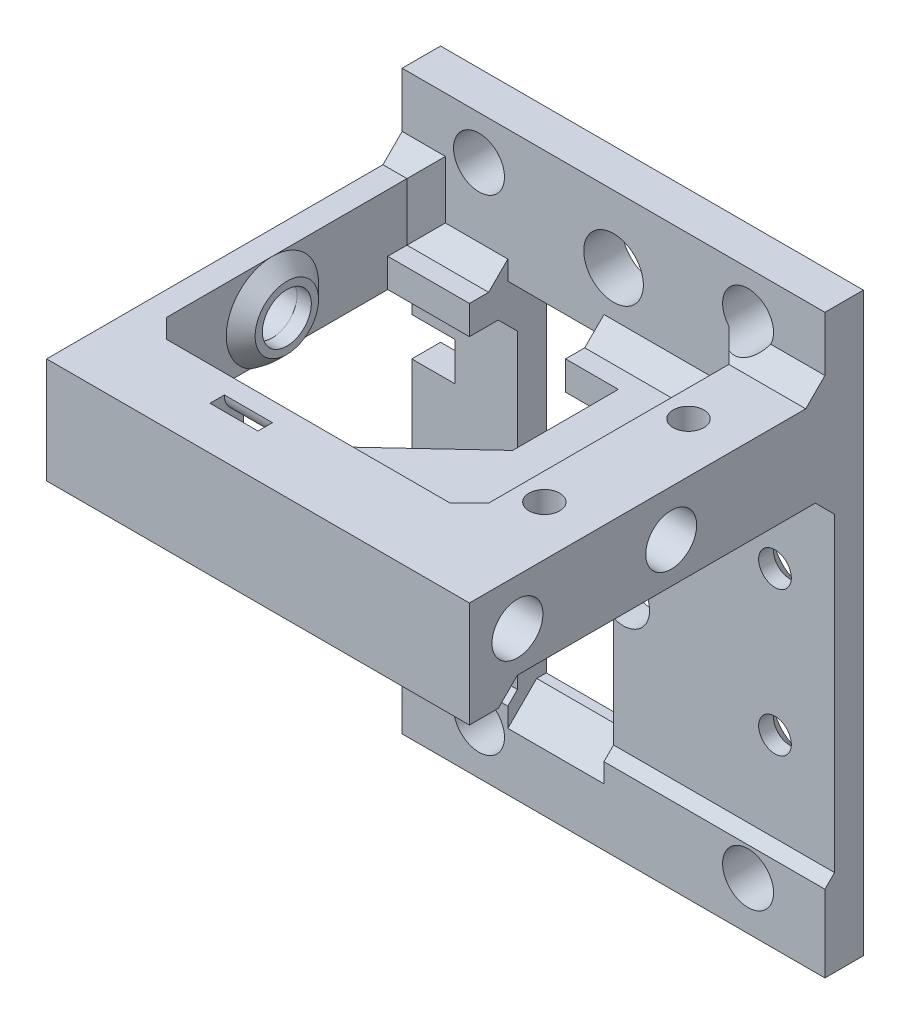
SolidWorks part; units mm, degrees
ref_plane "Front Plane" through (0, 0, 0) normal (0, 0, 1) x (1, 0, 0)
ref_plane "Top Plane" through (0, 0, 0) normal (0, 1, 0) x (1, 0, 0)
ref_plane "Right Plane" through (0, 0, 0) normal (1, 0, 0) x (0, 0, -1)
sketch "Sketch1" plane through (0, 0, 0) normal (0, 1, 0) x (1, 0, 0)
  line L0 (-19.5, 12.5) -> (-19.5, -12.5)
  line L1 (-22, -20.5) -> (22, -20.5)
  line L2 (-22, -20.5) -> (-22, 20.5)
  line L3 (-22, 20.5) -> (22, 20.5)
  line L4 (22, -20.5) -> (22, 20.5)
  line L5 (-22, -20.5) -> (22, 20.5) construction
  line L6 (-22, 20.5) -> (22, -20.5) construction
  line L7 (-19.5, 12.5) -> (4.5, 12.5)
  line L8 (4.5, 12.5) -> (4.5, 1.5)
  line L9 (-19.5, -12.5) -> (-10.5244, -12.5)
  line L10 (-10.5244, -12.5) -> (4.5, 1.5)
  circle A0 centre (16.8, -7.5) radius 1.6
  circle A1 centre (16.8, 7.5) radius 1.6
  point P0 (0, 0)
  dimension "D9" = 3.2
  dimension "D12" = 3.2
  dimension "D1" = 44
  dimension "D2" = 41
  dimension "D3" = 2.5
  dimension "D4" = 25
  dimension "D5" = 8
  dimension "D6" = 24
  dimension "D7" = 11
  dimension "D8" = 5.2
  dimension "D10" = 13
  dimension "D11" = 15
extrude "Boss-Extrude1" add sketch "Sketch1" along normal blind 3
sketch "Sketch2" plane through (0, 3, 0) normal (0, 1, 0) x (1, 0, 0)
  line L0 (-22, 20.5) -> (-22, -20.5) construction
  line L1 (22, 20.5) -> (-22, 20.5)
  line L2 (22, 20.5) -> (22, 16.5)
  line L3 (22, 16.5) -> (-22, 16.5)
  line L4 (-22, 20.5) -> (-22, 16.5)
  dimension "D1" = 4
extrude "Boss-Extrude2" add sketch "Sketch2" along normal blind 13.7
sketch "Sketch3" plane through (0, 0, 0) normal (0, -1, 0) x (1, 0, 0)
  line L0 (22, 20.5) -> (22, -20.5) construction
  line L1 (-22, -20.5) -> (22, -20.5)
  line L2 (-22, -20.5) -> (-22, -17.5)
  line L3 (-22, -17.5) -> (22, -17.5)
  line L4 (22, -20.5) -> (22, -17.5)
  dimension "D1" = 3
extrude "Boss-Extrude3" add sketch "Sketch3" along normal blind 41.3
sketch "Sketch4" plane through (0, 0, 0) normal (0, -1, 0) x (1, 0, 0)
  line L0 (-22, -17.5) -> (-22, 20.5) construction
  line L1 (22, 20.5) -> (-22, 20.5)
  line L2 (22, 20.5) -> (22, 17.5)
  line L3 (22, 17.5) -> (-22, 17.5)
  line L4 (-22, 20.5) -> (-22, 17.5)
  dimension "D1" = 3
extrude "Boss-Extrude4" add sketch "Sketch4" along normal blind 32.5
sketch "Sketch8" plane through (-22, 0, 0) normal (-1, 0, 0) x (0, 0, 1)
  line L0 (-16.5, -35.3) -> (-17.5, -34.3)
  line L1 (-17.5, -41.3) -> (-16.5, -41.3)
  line L2 (-17.5, -41.3) -> (-17.5, -35.3)
  line L3 (-17.5, -35.3) -> (-16.5, -35.3)
  line L4 (-16.5, -41.3) -> (-16.5, -35.3)
  line L5 (-17.5, -41.3) -> (-17.5, 0) construction
  line L6 (-17.5, -34.3) -> (-17.5, -35.3)
  line M5 (-17.5, -41.3) -> (-17.5, 0)
  dimension "D1" = 1
  dimension "D2" = 6
extrude "Boss-Extrude6" add sketch "Sketch8" against normal up to surface (44 mm away) contours L1 L4 L3 M5 | L3 L0 M5 region at (-22, -34.9667, -17.1667) region at (-22, -38.3, -17) up to face at (22, -10.82, -3.3)
sketch "Sketch9" plane through (0, 0, 20.5) normal (0, 0, 1) x (1, 0, 0)
  line L0 (-22, 3) -> (-22, -32.5) construction
  line L1 (3, -26) -> (10, -26)
  line L2 (3, -26) -> (3, -5)
  line L3 (3, -5) -> (10, -5)
  line L4 (10, -26) -> (10, -5)
  line L5 (22, -32.5) -> (-22, -32.5) construction
  line L6 (22, 3) -> (22, -32.5) construction
  circle A0 centre (15.8, -10) radius 1.6
  circle A1 centre (15.8, -25) radius 1.6
  dimension "D5" = 3.2
  dimension "D6" = 3.2
  dimension "D1" = 25
  dimension "D2" = 7
  dimension "D3" = 21
  dimension "D4" = 6.5
  dimension "D7" = 6.2
  dimension "D8" = 6.2
  dimension "D9" = 15
  dimension "D10" = 7.5
extrude "Cut-Extrude2" cut sketch "Sketch9" against normal up to next
sketch "Sketch12" plane through (0, 3, 0) normal (0, 1, 0) x (1, 0, 0)
  line L0 (-22, 16.5) -> (-22, -20.5) construction
  line L1 (22, -20.5) -> (-22, -20.5)
  line L2 (22, -20.5) -> (22, -12.5)
  line L3 (22, -12.5) -> (-22, -12.5)
  line L4 (-22, -20.5) -> (-22, -12.5)
  line L5 (-19.5, -12.5) -> (-10.5244, -12.5) construction
  line L6 (-19.5, 12.5) -> (-19.5, -12.5) construction
  line L7 (-22, 16.5) -> (-19.5, 16.5)
  line L8 (-22, 16.5) -> (-22, -12.5)
  line L9 (-22, -12.5) -> (-19.5, -12.5)
  line L10 (-19.5, 16.5) -> (-19.5, -12.5)
  line L11 (-22, 16.5) -> (22, 16.5) construction
  line L12 (22, -12.5) -> (14, -12.5)
  line L13 (22, -12.5) -> (22, 16.5)
  line L14 (22, 16.5) -> (14, 16.5)
  line L15 (14, -12.5) -> (14, 16.5)
  circle M6 centre (16.8, 7.5) radius 1.6
  circle M7 centre (16.8, -7.5) radius 1.6
  line M11 (-10.5244, -12.5) -> (-19.5, -12.5)
  line M12 (-19.5, -12.5) -> (-19.5, 12.5)
  line M13 (22, 16.5) -> (-22, 16.5)
  line M14 (-22, 16.5) -> (-22, -20.5)
  line M15 (-22, -20.5) -> (22, -20.5)
  line M16 (22, -20.5) -> (22, 16.5)
  dimension "D1" = 8
extrude "Boss-Extrude7" add sketch "Sketch12" along normal blind 6 contours L15 L3 M16 M13 M7 M6 | L3 M16 M11 M14 M15 | L10 L3 M13 M14 M12 region at (0, 3, 16.5) region at (18.0894, 3, -2.149) region at (-20.75, 3, -2)
sketch "Sketch13" plane through (-22, 0, 0) normal (-1, 0, 0) x (0, 0, 1)
  line L0 (20.5, 9) -> (20.5, -32.5) construction
  line L1 (-17.5, 0) -> (17.5, 0) construction
  line L2 (-17.5, -34.3) -> (-17.5, 0) construction
  circle A0 centre (15.5, 4.2) radius 2.65
  circle A1 centre (-0.5, 4.2) radius 2.65
  dimension "D3" = 5.3
  dimension "D5" = 5.3
  dimension "D1" = 5
  dimension "D2" = 4.2
  dimension "D4" = 17
extrude "Cut-Extrude3" cut sketch "Sketch13" against normal blind 6
sketch "Sketch14" plane through (-19.5, 0, 0) normal (1, 0, 0) x (0, 0, -1)
  circle A0 centre (0.5, 4.2) radius 3.3
  circle A1 centre (0.5, 4.2) radius 2.55
  dimension "D1" = 6.6
extrude "Boss-Extrude9" add sketch "Sketch14" along normal blind 1.5
mirror "Mirror1" about plane through (0, 0, 0) normal (1, 0, 0) of "Cut-Extrude3"
sketch "Sketch15" plane through (0, 0, 20.5) normal (0, 0, 1) x (1, 0, 0)
  point P0 (15.8, -10)
  point P1 (15.8, -25)
hole_wizard "CSK for M3 Flat Head Machine Screw1" positions "Sketch18" profile "Sketch19" countersink size "M3" standard "ANSI Metric" end condition through all
sketch "Sketch18" plane through (0, 0, 20.5) normal (0, 0, 1) x (1, 0, 0)
  point P0 (15.8, -10)
  point P3 (15.8, -25)
sketch "Sketch19" plane through (15.8, -10, 20.5) normal (1, 0, 0) x (0, -1, 0)
  line L0 (0, 0) -> (0, 41)
  line L1 (0, 41) -> (1.7, 41)
  line L2 (1.7, 41) -> (1.7, 1.45)
  line L3 (1.7, 1.45) -> (3.15, 0)
  line L5 (3.15, 0) -> (0, 0)
  line L6 (-1.7, 1.45) -> (-3.15, 0) construction
  line L11 (0, -6.35) -> (0, 107.95) construction
  dimension "Thru Hole Dia." = 3.4
  dimension "Thru Hole Depth" = 41
  dimension "Near C'Sink Dia." = 6.3
  dimension "Near C'Sink Angle" = 90
sketch "Sketch20" plane through (0, 0, -20.5) normal (0, 0, -1) x (-1, 0, 0)
  point P0 (-15.8, -10)
  point P1 (-15.8, -25)
hole_wizard "CSK for M3 Flat Head Machine Screw2" positions "Sketch21" profile "Sketch22" countersink size "M3" standard "ANSI Metric" end condition through all
sketch "Sketch21" plane through (0, 0, -20.5) normal (0, 0, -1) x (-1, 0, 0)
  point P0 (-15.8, -10)
  point P3 (-15.8, -25)
sketch "Sketch22" plane through (15.8, -10, -20.5) normal (1, 0, 0) x (0, 1, 0)
  line L0 (0, 0) -> (0, 41)
  line L1 (0, 41) -> (1.7, 41)
  line L2 (1.7, 41) -> (1.7, 1.45)
  line L3 (1.7, 1.45) -> (3.15, 0)
  line L5 (3.15, 0) -> (0, 0)
  line L6 (-1.7, 1.45) -> (-3.15, 0) construction
  line L11 (0, -6.35) -> (0, 107.95) construction
  dimension "Thru Hole Dia." = 3.4
  dimension "Thru Hole Depth" = 41
  dimension "Near C'Sink Dia." = 6.3
  dimension "Near C'Sink Angle" = 90
sketch "Sketch23" plane through (0, 0, -17.5) normal (0, 0, 1) x (1, 0, 0)
  line L0 (22, -34.3) -> (-22, -34.3) construction
  line L1 (-1, 3) -> (-11, 3)
  line L2 (-1, 3) -> (-1, -34.3)
  line L3 (-1, -34.3) -> (-11, -34.3)
  line L4 (-11, 3) -> (-11, -34.3)
  line L5 (-1, 3) -> (-11, -34.3) construction
  line L6 (-1, -34.3) -> (-11, 3) construction
  line L9 (-22, -34.3) -> (-22, 0) construction
  line L11 (14, 3) -> (-10.5244, 3) construction
  point P0 (-6, -15.65)
  dimension "D2" = 16
extrude "Cut-Extrude4" cut sketch "Sketch23" against normal up to next and the other way up to next
chamfer "Chamfer2" distance 1.5 1 edges at (-19.5, 4.2, -3.8)
chamfer "Chamfer3" distance 2 11 edges at (-15.25, 3, -16.5) (6.5, 3, -16.5) (10.5, 0, -17.5) (-16.5, 0, -17.5) (0, 0, 17.5) (18, 9, -16.5) (-20.75, 9, -16.5) (-19.5, 4.5, 12.5) (14, 6, 12.5) (14, 6, -16.5) (-19.5, 6, -16.5)
sketch "Sketch5" plane through (0, 0, -20.5) normal (0, 0, -1) x (-1, 0, 0)
  line L0 (0, -41.3) -> (0, 16.7) construction
  line L1 (22, -41.3) -> (-22, -41.3) construction
  line L2 (-22, 16.7) -> (22, 16.7) construction
  circle A0 centre (-14, -38.3) radius 2.65
  circle A1 centre (14, -38.3) radius 2.65
  circle A2 centre (-14, 12.2) radius 2.65
  circle A3 centre (14, 12.2) radius 2.65
  circle A4 centre (0, 9.7) radius 3.1
  circle A5 centre (0, -20.3) radius 2.75
  dimension "D1" = 5.3
  dimension "D4" = 5.3
  dimension "D7" = 6.2
  dimension "D8" = 37
  dimension "D9" = 5.5
  dimension "D2" = 3
  dimension "D3" = 14
  dimension "D5" = 50.5
  dimension "D6" = 7
extrude "Cut-Extrude1" cut sketch "Sketch5" against normal up to next
sketch "Sketch24" plane through (-1, 0, 0) normal (-1, 0, 0) x (0, 0, 1)
  line L3 (-17.5, -34.3) -> (-19.5, -34.3)
  line L5 (-16.5, -40.95) -> (-16.5, -35.65) construction
  line L6 (-16.5, -37.3) -> (-16.5, -35.3)
  line L7 (-16.5, -41.3) -> (-16.5, -35.3) construction
  line L8 (-19.5, -34.3) -> (-16.5, -37.3)
  line L9 (-16.5, -35.3) -> (-17.5, -34.3)
extrude "Cut-Extrude9" cut sketch "Sketch24" along normal up to surface (10 mm away) up to face at (-11, -5.36, -16.4)
sketch "Sketch25" plane through (0, 0, 12.5) normal (0, 0, -1) x (-1, 0, 0)
  line L0 (22, 16.7) -> (22, -41.3) construction
  line L1 (9.5, 7) -> (4.5, 7)
  line L2 (9.5, 7) -> (9.5, 5.5)
  line L3 (9.5, 5.5) -> (4.5, 5.5)
  line L4 (4.5, 7) -> (4.5, 5.5)
  line L5 (9.5, 7) -> (4.5, 5.5) construction
  line L6 (9.5, 5.5) -> (4.5, 7) construction
  line L7 (-12, 9) -> (17.5, 9) construction
  point P0 (7, 6.25)
  dimension "D1" = 15
  dimension "D2" = 5
  dimension "D3" = 1.5
  dimension "D4" = 2
sketch "Sketch26" plane through (0, 0, -20.5) normal (0, 0, -1) x (-1, 0, 0)
  line L0 (22, 16.7) -> (22, -41.3) construction
  line L1 (22, -6) -> (17.5, -6)
  line L2 (22, -6) -> (22, -10)
  line L3 (22, -10) -> (17.5, -10)
  line L4 (17.5, -6) -> (17.5, -10)
  line L6 (22.55, 0) -> (-22.55, 0) construction
  dimension "D1" = 6
  dimension "D2" = 4
  dimension "D3" = 4.5
extrude "Cut-Extrude11" cut sketch "Sketch26" against normal up to next
revolve "Cut-Revolve1" cut sketch "Sketch25" angle 90 about axis through (0, 9, 12.5) along (-1, 0, 0)
sketch "Sketch27" plane through (0, -41.3, 0) normal (0, -1, 0) x (1, 0, 0)
  line L1 (-22, -20.5) -> (22, -20.5)
  line L2 (-22, -20.5) -> (-22, -16.5)
  line L3 (-22, -16.5) -> (22, -16.5)
  line L4 (22, -20.5) -> (22, -16.5)
extrude "Boss-Extrude10" add sketch "Sketch27" along normal blind 2
sketch "Sketch28" plane through (0, -32.5, 0) normal (0, -1, 0) x (1, 0, 0)
  line L1 (-22, 17.5) -> (22, 17.5)
  line L2 (-22, 17.5) -> (-22, 20.5)
  line L3 (-22, 20.5) -> (22, 20.5)
  line L4 (22, 17.5) -> (22, 20.5)
extrude "Cut-Extrude13" cut sketch "Sketch28" against normal blind 30.5
